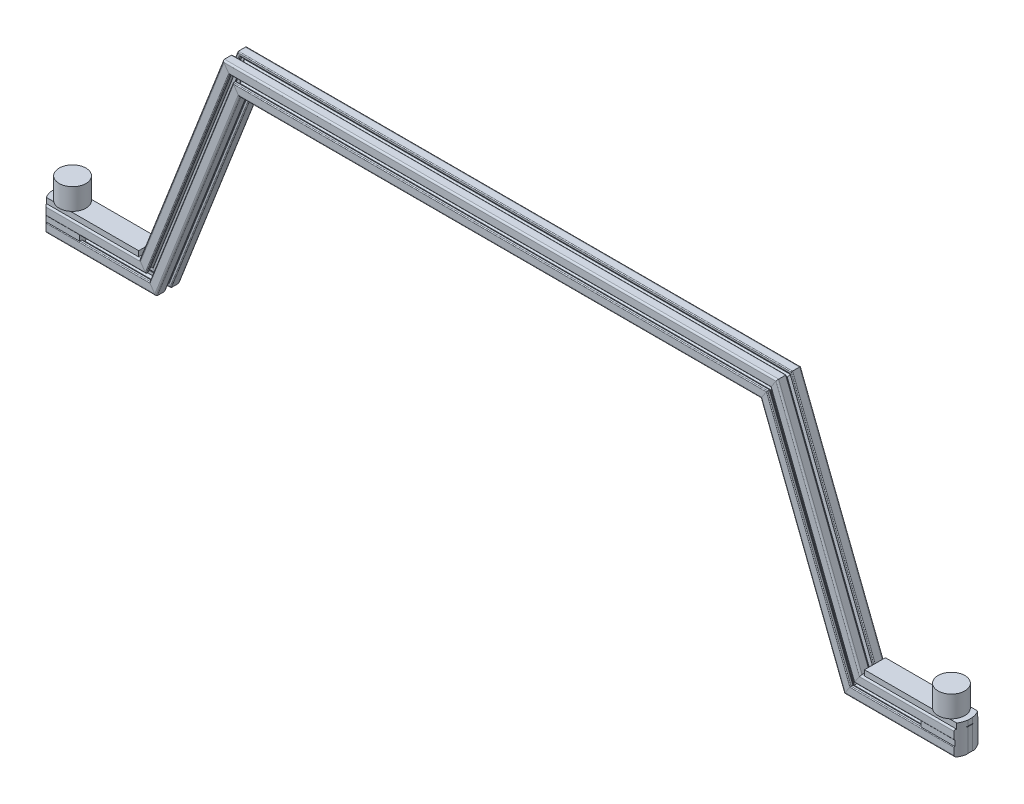
SolidWorks part; units mm, degrees
material "Commercially Pure CP-Ti UNS R50400 (SS)"
ref_plane "Front Plane" through (0, 0, 0) normal (0, 0, 1) x (1, 0, 0)
ref_plane "Top Plane" through (0, 0, 0) normal (0, 1, 0) x (1, 0, 0)
ref_plane "Right Plane" through (0, 0, 0) normal (1, 0, 0) x (0, 0, -1)
sketch "Sketch7" plane through (0, 0, 0) normal (1, 0, 0) x (0, 0, -1)
  line L0 (13.9698, 21.2743) -> (13.5298, 21.2743)
  line L1 (12.0298, 22.7743) -> (12.0298, 23.2743)
  line L2 (13.5298, 24.7743) -> (23.1398, 24.7743)
  line L3 (25.4198, 22.4943) -> (25.4198, 12.8843)
  line L4 (23.9198, 11.3843) -> (23.4198, 11.3843)
  line L5 (21.9198, 12.8843) -> (21.9198, 13.3243)
  line L6 (20.9198, 14.3243) -> (15.3498, 14.3243)
  line L7 (14.9698, 14.7043) -> (14.9698, 20.2743)
  line L8 (21.9589, -6.6897) -> (21.9589, -6.2497)
  line L9 (23.4589, -4.7497) -> (23.9589, -4.7497)
  line L10 (25.4589, -6.2497) -> (25.4589, -15.8597)
  line L11 (23.1789, -18.1397) -> (13.5689, -18.1397)
  line L12 (12.0689, -16.6397) -> (12.0689, -16.1397)
  line L13 (13.5689, -14.6397) -> (14.0089, -14.6397)
  line L14 (15.0089, -13.6397) -> (15.0089, -8.0697)
  line L15 (15.3889, -7.6897) -> (20.9589, -7.6897)
  line L16 (-6.0052, -14.6787) -> (-5.5652, -14.6787)
  line L17 (-4.0652, -16.1787) -> (-4.0652, -16.6787)
  line L18 (-5.5652, -18.1787) -> (-15.1752, -18.1787)
  line L19 (-17.4552, -15.8987) -> (-17.4552, -6.2887)
  line L20 (-15.9552, -4.7887) -> (-15.4552, -4.7887)
  line L21 (-13.9552, -6.2887) -> (-13.9552, -6.7287)
  line L22 (-12.9552, -7.7287) -> (-7.3852, -7.7287)
  line L23 (-7.0052, -8.1087) -> (-7.0052, -13.6787)
  line L24 (1.8289, -2.4886) -> (1.4132, -2.3164)
  line L25 (-1.632, 0.7289) -> (-1.8042, 1.1447)
  line L26 (-1.804, 5.4512) -> (-1.6318, 5.867)
  line L27 (1.4134, 8.9121) -> (1.8292, 9.0843)
  line L28 (6.1358, 9.0842) -> (6.5515, 8.912)
  line L29 (9.5966, 5.8667) -> (9.7688, 5.451)
  line L30 (9.7687, 1.1444) -> (9.5965, 0.7287)
  line L31 (6.5512, -2.3165) -> (6.1355, -2.4887)
  line L32 (-13.9942, 13.2853) -> (-13.9942, 12.8453)
  line L33 (-15.4942, 11.3453) -> (-15.9942, 11.3453)
  line L34 (-17.4942, 12.8453) -> (-17.4942, 22.4553)
  line L35 (-15.2142, 24.7353) -> (-5.6042, 24.7353)
  line L36 (-4.1042, 23.2353) -> (-4.1042, 22.7353)
  line L37 (-5.6042, 21.2353) -> (-6.0442, 21.2353)
  line L38 (-7.0442, 20.2353) -> (-7.0442, 14.6653)
  line L39 (-7.4242, 14.2853) -> (-12.9942, 14.2853)
  line L40 (4.9058, 11.2153) -> (4.0058, 10.7002)
  line L41 (4.0058, 10.7002) -> (3.1058, 11.2153)
  line L42 (3.1058, 11.2153) -> (-2.1975, 11.2153)
  line L43 (-2.4662, 11.3266) -> (-5.9329, 14.7933)
  line L44 (-6.0442, 15.062) -> (-6.0442, 19.3553)
  line L45 (-5.6642, 19.7353) -> (-2.5792, 19.7353)
  line L46 (-1.0592, 21.2553) -> (-1.0592, 24.2153)
  line L47 (-2.5792, 25.7353) -> (-15.4942, 25.7353)
  line L48 (-18.4942, 22.7353) -> (-18.4942, 9.8203)
  line L49 (-16.9742, 8.3003) -> (-14.0142, 8.3003)
  line L50 (-12.4942, 9.8203) -> (-12.4942, 12.9053)
  line L51 (-12.1142, 13.2853) -> (-7.8138, 13.2853)
  line L52 (-7.5451, 13.174) -> (-4.0855, 9.7144)
  line L53 (-3.9742, 9.4457) -> (-3.9742, 4.1353)
  line L54 (-3.9742, 4.1353) -> (-3.4546, 3.2353)
  line L55 (-3.4546, 3.2353) -> (-3.9742, 2.3353)
  line L56 (-3.9742, 2.3353) -> (-3.9742, -2.968)
  line L57 (-4.0855, -3.2367) -> (-7.5522, -6.7034)
  line L58 (-7.8209, -6.8147) -> (-12.1142, -6.8147)
  line L59 (-12.4942, -6.4347) -> (-12.4942, -3.3497)
  line L60 (-14.0142, -1.8297) -> (-16.9742, -1.8297)
  line L61 (-18.4942, -3.3497) -> (-18.4942, -16.2647)
  line L62 (-15.4942, -19.2647) -> (-2.5792, -19.2647)
  line L63 (-1.0592, -17.7447) -> (-1.0592, -14.7847)
  line L64 (-2.5792, -13.2647) -> (-5.6642, -13.2647)
  line L65 (-6.0442, -12.8847) -> (-6.0442, -8.5843)
  line L66 (-5.9329, -8.3156) -> (-2.4733, -4.856)
  line L67 (-2.2046, -4.7447) -> (3.1058, -4.7447)
  line L68 (3.1058, -4.7447) -> (4.0058, -4.2295)
  line L69 (4.0058, -4.2295) -> (4.9058, -4.7447)
  line L70 (4.9058, -4.7447) -> (10.2091, -4.7447)
  line L71 (10.4778, -4.856) -> (13.9445, -8.3227)
  line L72 (14.0558, -8.5914) -> (14.0558, -12.8847)
  line L73 (13.6758, -13.2647) -> (10.5908, -13.2647)
  line L74 (9.0708, -14.7847) -> (9.0708, -17.7447)
  line L75 (10.5908, -19.2647) -> (23.5058, -19.2647)
  line L76 (26.5058, -16.2647) -> (26.5058, -3.3497)
  line L77 (24.9858, -1.8297) -> (22.0258, -1.8297)
  line L78 (20.5058, -3.3497) -> (20.5058, -6.4347)
  line L79 (20.1258, -6.8147) -> (15.8254, -6.8147)
  line L80 (15.5567, -6.7034) -> (12.0971, -3.2438)
  line L81 (11.9858, -2.9751) -> (11.9858, 2.3353)
  line L82 (11.9858, 2.3353) -> (11.4662, 3.2353)
  line L83 (11.4662, 3.2353) -> (11.9858, 4.1353)
  line L84 (11.9858, 4.1353) -> (11.9858, 9.4386)
  line L85 (12.0971, 9.7073) -> (15.5638, 13.174)
  line L86 (15.8325, 13.2853) -> (20.1258, 13.2853)
  line L87 (20.5058, 12.9053) -> (20.5058, 9.8203)
  line L88 (22.0258, 8.3003) -> (24.9858, 8.3003)
  line L89 (26.5058, 9.8203) -> (26.5058, 22.7353)
  line L90 (23.5058, 25.7353) -> (10.5908, 25.7353)
  line L91 (9.0708, 24.2153) -> (9.0708, 21.2553)
  line L92 (10.5908, 19.7353) -> (13.6758, 19.7353)
  line L93 (14.0558, 19.3553) -> (14.0558, 15.0549)
  line L94 (13.9445, 14.7862) -> (10.4849, 11.3266)
  line L95 (10.2162, 11.2153) -> (4.9058, 11.2153)
  arc A0 (14.9698, 20.2743) -> (13.9698, 21.2743) centre (13.9698, 20.2743) ccw
  arc A1 (12.0298, 22.7743) -> (13.5298, 21.2743) centre (13.5298, 22.7743) ccw
  arc A2 (13.5298, 24.7743) -> (12.0298, 23.2743) centre (13.5298, 23.2743) ccw
  arc A3 (25.4198, 22.4943) -> (23.1398, 24.7743) centre (23.1398, 22.4943) ccw
  arc A4 (23.9198, 11.3843) -> (25.4198, 12.8843) centre (23.9198, 12.8843) ccw
  arc A5 (21.9198, 12.8843) -> (23.4198, 11.3843) centre (23.4198, 12.8843) ccw
  arc A6 (21.9198, 13.3243) -> (20.9198, 14.3243) centre (20.9198, 13.3243) ccw
  arc A7 (14.9698, 14.7043) -> (15.3498, 14.3243) centre (15.3498, 14.7043) ccw
  arc A8 (20.9589, -7.6897) -> (21.9589, -6.6897) centre (20.9589, -6.6897) ccw
  arc A9 (23.4589, -4.7497) -> (21.9589, -6.2497) centre (23.4589, -6.2497) ccw
  arc A10 (25.4589, -6.2497) -> (23.9589, -4.7497) centre (23.9589, -6.2497) ccw
  arc A11 (23.1789, -18.1397) -> (25.4589, -15.8597) centre (23.1789, -15.8597) ccw
  arc A12 (12.0689, -16.6397) -> (13.5689, -18.1397) centre (13.5689, -16.6397) ccw
  arc A13 (13.5689, -14.6397) -> (12.0689, -16.1397) centre (13.5689, -16.1397) ccw
  arc A14 (14.0089, -14.6397) -> (15.0089, -13.6397) centre (14.0089, -13.6397) ccw
  arc A15 (15.3889, -7.6897) -> (15.0089, -8.0697) centre (15.3889, -8.0697) ccw
  arc A16 (-7.0052, -13.6787) -> (-6.0052, -14.6787) centre (-6.0052, -13.6787) ccw
  arc A17 (-4.0652, -16.1787) -> (-5.5652, -14.6787) centre (-5.5652, -16.1787) ccw
  arc A18 (-5.5652, -18.1787) -> (-4.0652, -16.6787) centre (-5.5652, -16.6787) ccw
  arc A19 (-17.4552, -15.8987) -> (-15.1752, -18.1787) centre (-15.1752, -15.8987) ccw
  arc A20 (-15.9552, -4.7887) -> (-17.4552, -6.2887) centre (-15.9552, -6.2887) ccw
  arc A21 (-13.9552, -6.2887) -> (-15.4552, -4.7887) centre (-15.4552, -6.2887) ccw
  arc A22 (-13.9552, -6.7287) -> (-12.9552, -7.7287) centre (-12.9552, -6.7287) ccw
  arc A23 (-7.0052, -8.1087) -> (-7.3852, -7.7287) centre (-7.3852, -8.1087) ccw
  arc A24 (1.0363, -0.7421) -> (1.4132, -2.3164) centre (1.7959, -1.3925) ccw
  arc A25 (-0.0577, 0.352) -> (1.0363, -0.7421) centre (3.9823, 3.2978) ccw
  arc A26 (-1.632, 0.7289) -> (-0.0577, 0.352) centre (-0.7081, 1.1116) ccw
  arc A27 (-0.9575, 2.5244) -> (-1.8042, 1.1447) centre (-0.8803, 1.5274) ccw
  arc A28 (-0.9574, 4.0715) -> (-0.9575, 2.5244) centre (3.9823, 3.2978) ccw
  arc A29 (-1.804, 5.4512) -> (-0.9574, 4.0715) centre (-0.8802, 5.0686) ccw
  arc A30 (-0.0575, 6.2439) -> (-1.6318, 5.867) centre (-0.708, 5.4843) ccw
  arc A31 (1.0365, 7.3379) -> (-0.0575, 6.2439) centre (3.9823, 3.2978) ccw
  arc A32 (1.4134, 8.9121) -> (1.0365, 7.3379) centre (1.7961, 7.9882) ccw
  arc A33 (3.2089, 8.2376) -> (1.8292, 9.0843) centre (2.2119, 8.1604) ccw
  arc A34 (4.7561, 8.2376) -> (3.2089, 8.2376) centre (3.9823, 3.2978) ccw
  arc A35 (6.1358, 9.0842) -> (4.7561, 8.2376) centre (5.7531, 8.1603) ccw
  arc A36 (6.9284, 7.3377) -> (6.5515, 8.912) centre (6.1688, 7.9881) ccw
  arc A37 (8.0224, 6.2437) -> (6.9284, 7.3377) centre (3.9823, 3.2978) ccw
  arc A38 (9.5966, 5.8667) -> (8.0224, 6.2437) centre (8.6727, 5.484) ccw
  arc A39 (8.9222, 4.0713) -> (9.7688, 5.451) centre (8.845, 5.0683) ccw
  arc A40 (8.9221, 2.5241) -> (8.9222, 4.0713) centre (3.9823, 3.2978) ccw
  arc A41 (9.7687, 1.1444) -> (8.9221, 2.5241) centre (8.8448, 1.5271) ccw
  arc A42 (8.0222, 0.3518) -> (9.5965, 0.7287) centre (8.6726, 1.1113) ccw
  arc A43 (6.9282, -0.7422) -> (8.0222, 0.3518) centre (3.9823, 3.2978) ccw
  arc A44 (6.5512, -2.3165) -> (6.9282, -0.7422) centre (6.1685, -1.3926) ccw
  arc A45 (4.7558, -1.642) -> (6.1355, -2.4887) centre (5.7528, -1.5648) ccw
  arc A46 (3.2086, -1.642) -> (4.7558, -1.642) centre (3.9823, 3.2978) ccw
  arc A47 (1.8289, -2.4886) -> (3.2086, -1.642) centre (2.2116, -1.5647) ccw
  arc A48 (-12.9942, 14.2853) -> (-13.9942, 13.2853) centre (-12.9942, 13.2853) ccw
  arc A49 (-15.4942, 11.3453) -> (-13.9942, 12.8453) centre (-15.4942, 12.8453) ccw
  arc A50 (-17.4942, 12.8453) -> (-15.9942, 11.3453) centre (-15.9942, 12.8453) ccw
  arc A51 (-15.2142, 24.7353) -> (-17.4942, 22.4553) centre (-15.2142, 22.4553) ccw
  arc A52 (-4.1042, 23.2353) -> (-5.6042, 24.7353) centre (-5.6042, 23.2353) ccw
  arc A53 (-5.6042, 21.2353) -> (-4.1042, 22.7353) centre (-5.6042, 22.7353) ccw
  arc A54 (-6.0442, 21.2353) -> (-7.0442, 20.2353) centre (-6.0442, 20.2353) ccw
  arc A55 (-7.4242, 14.2853) -> (-7.0442, 14.6653) centre (-7.4242, 14.6653) ccw
  arc A56 (-2.4662, 11.3266) -> (-2.1975, 11.2153) centre (-2.1975, 11.5953) ccw
  arc A57 (-6.0442, 15.062) -> (-5.9329, 14.7933) centre (-5.6642, 15.062) ccw
  arc A58 (-5.6642, 19.7353) -> (-6.0442, 19.3553) centre (-5.6642, 19.3553) ccw
  arc A59 (-2.5792, 19.7353) -> (-1.0592, 21.2553) centre (-2.5792, 21.2553) ccw
  arc A60 (-1.0592, 24.2153) -> (-2.5792, 25.7353) centre (-2.5792, 24.2153) ccw
  arc A61 (-15.4942, 25.7353) -> (-18.4942, 22.7353) centre (-15.4942, 22.7353) ccw
  arc A62 (-18.4942, 9.8203) -> (-16.9742, 8.3003) centre (-16.9742, 9.8203) ccw
  arc A63 (-14.0142, 8.3003) -> (-12.4942, 9.8203) centre (-14.0142, 9.8203) ccw
  arc A64 (-12.1142, 13.2853) -> (-12.4942, 12.9053) centre (-12.1142, 12.9053) ccw
  arc A65 (-7.5451, 13.174) -> (-7.8138, 13.2853) centre (-7.8138, 12.9053) ccw
  arc A66 (-3.9742, 9.4457) -> (-4.0855, 9.7144) centre (-4.3542, 9.4457) ccw
  arc A67 (-4.0855, -3.2367) -> (-3.9742, -2.968) centre (-4.3542, -2.968) ccw
  arc A68 (-7.8209, -6.8147) -> (-7.5522, -6.7034) centre (-7.8209, -6.4347) ccw
  arc A69 (-12.4942, -6.4347) -> (-12.1142, -6.8147) centre (-12.1142, -6.4347) ccw
  arc A70 (-12.4942, -3.3497) -> (-14.0142, -1.8297) centre (-14.0142, -3.3497) ccw
  arc A71 (-16.9742, -1.8297) -> (-18.4942, -3.3497) centre (-16.9742, -3.3497) ccw
  arc A72 (-18.4942, -16.2647) -> (-15.4942, -19.2647) centre (-15.4942, -16.2647) ccw
  arc A73 (-2.5792, -19.2647) -> (-1.0592, -17.7447) centre (-2.5792, -17.7447) ccw
  arc A74 (-1.0592, -14.7847) -> (-2.5792, -13.2647) centre (-2.5792, -14.7847) ccw
  arc A75 (-6.0442, -12.8847) -> (-5.6642, -13.2647) centre (-5.6642, -12.8847) ccw
  arc A76 (-5.9329, -8.3156) -> (-6.0442, -8.5843) centre (-5.6642, -8.5843) ccw
  arc A77 (-2.2046, -4.7447) -> (-2.4733, -4.856) centre (-2.2046, -5.1247) ccw
  arc A78 (10.4778, -4.856) -> (10.2091, -4.7447) centre (10.2091, -5.1247) ccw
  arc A79 (14.0558, -8.5914) -> (13.9445, -8.3227) centre (13.6758, -8.5914) ccw
  arc A80 (13.6758, -13.2647) -> (14.0558, -12.8847) centre (13.6758, -12.8847) ccw
  arc A81 (10.5908, -13.2647) -> (9.0708, -14.7847) centre (10.5908, -14.7847) ccw
  arc A82 (9.0708, -17.7447) -> (10.5908, -19.2647) centre (10.5908, -17.7447) ccw
  arc A83 (23.5058, -19.2647) -> (26.5058, -16.2647) centre (23.5058, -16.2647) ccw
  arc A84 (26.5058, -3.3497) -> (24.9858, -1.8297) centre (24.9858, -3.3497) ccw
  arc A85 (22.0258, -1.8297) -> (20.5058, -3.3497) centre (22.0258, -3.3497) ccw
  arc A86 (20.1258, -6.8147) -> (20.5058, -6.4347) centre (20.1258, -6.4347) ccw
  arc A87 (15.5567, -6.7034) -> (15.8254, -6.8147) centre (15.8254, -6.4347) ccw
  arc A88 (11.9858, -2.9751) -> (12.0971, -3.2438) centre (12.3658, -2.9751) ccw
  arc A89 (12.0971, 9.7073) -> (11.9858, 9.4386) centre (12.3658, 9.4386) ccw
  arc A90 (15.8325, 13.2853) -> (15.5638, 13.174) centre (15.8325, 12.9053) ccw
  arc A91 (20.5058, 12.9053) -> (20.1258, 13.2853) centre (20.1258, 12.9053) ccw
  arc A92 (20.5058, 9.8203) -> (22.0258, 8.3003) centre (22.0258, 9.8203) ccw
  arc A93 (24.9858, 8.3003) -> (26.5058, 9.8203) centre (24.9858, 9.8203) ccw
  arc A94 (26.5058, 22.7353) -> (23.5058, 25.7353) centre (23.5058, 22.7353) ccw
  arc A95 (10.5908, 25.7353) -> (9.0708, 24.2153) centre (10.5908, 24.2153) ccw
  arc A96 (9.0708, 21.2553) -> (10.5908, 19.7353) centre (10.5908, 21.2553) ccw
  arc A97 (14.0558, 19.3553) -> (13.6758, 19.7353) centre (13.6758, 19.3553) ccw
  arc A98 (13.9445, 14.7862) -> (14.0558, 15.0549) centre (13.6758, 15.0549) ccw
  arc A99 (10.2162, 11.2153) -> (10.4849, 11.3266) centre (10.2162, 11.5953) ccw
sketch "Sketch1" plane through (0, 0, 0) normal (0, 0, 1) x (1, 0, 0)
  line L0 (0, 0) -> (200, 0)
  line L1 (200, 0) -> (355.8974, 400)
  line L2 (355.8974, 400) -> (855.8974, 400)
  dimension "D1" = 500
  dimension "D2" = 200
  dimension "D3" = 400
sketch "Sketch2" [suppressed] plane through (0, 0, 0) normal (1, 0, 0) x (0, 0, -1)
  line L0 (-33.5, -41) -> (-31.5, -41)
  line L1 (-31.5, -43) -> (-42, -43)
  line L2 (-43, -42) -> (-43, -31.5)
  line L3 (-41, -31.5) -> (-41, -33.5)
  line L4 (-40, -34.5) -> (-34.88, -34.5)
  line L5 (-34.5, -34.88) -> (-34.5, -40)
  line L6 (-16.657, -26.2238) -> (-18.284, -25.188)
  line L7 (-19.8123, -26.7162) -> (-18.7764, -28.3429)
  line L8 (-21.0015, -29.2647) -> (-21.4195, -27.3819)
  line L9 (-23.5808, -27.3818) -> (-23.9986, -29.2645)
  line L10 (-26.2238, -28.343) -> (-25.188, -26.716)
  line L11 (-26.7162, -25.1877) -> (-28.3429, -26.2236)
  line L12 (-29.2647, -23.9985) -> (-27.3819, -23.5805)
  line L13 (-27.3818, -21.4192) -> (-29.2645, -21.0014)
  line L14 (-28.343, -18.7762) -> (-26.716, -19.812)
  line L15 (-25.1877, -18.2838) -> (-26.2236, -16.6571)
  line L16 (-23.9985, -15.7353) -> (-23.5805, -17.6181)
  line L17 (-21.4192, -17.6182) -> (-21.0014, -15.7355)
  line L18 (-18.7762, -16.657) -> (-19.812, -18.284)
  line L19 (-18.2838, -19.8123) -> (-16.6571, -18.7764)
  line L20 (-15.7353, -21.0015) -> (-17.6181, -21.4195)
  line L21 (-17.6182, -23.5808) -> (-15.7355, -23.9986)
  line L22 (41, -33.5) -> (41, -31.5)
  line L23 (43, -31.5) -> (43, -42)
  line L24 (42, -43) -> (31.5, -43)
  line L25 (31.5, -41) -> (33.5, -41)
  line L26 (34.5, -40) -> (34.5, -34.88)
  line L27 (34.88, -34.5) -> (40, -34.5)
  line L28 (26.7162, -19.8123) -> (28.3429, -18.7764)
  line L29 (29.2647, -21.0015) -> (27.3819, -21.4195)
  line L30 (27.3818, -23.5808) -> (29.2645, -23.9986)
  line L31 (28.343, -26.2238) -> (26.716, -25.188)
  line L32 (25.1877, -26.7162) -> (26.2236, -28.3429)
  line L33 (23.9985, -29.2647) -> (23.5805, -27.3819)
  line L34 (21.4192, -27.3818) -> (21.0014, -29.2645)
  line L35 (18.7762, -28.343) -> (19.812, -26.716)
  line L36 (18.2838, -25.1877) -> (16.6571, -26.2236)
  line L37 (15.7353, -23.9985) -> (17.6181, -23.5805)
  line L38 (17.6182, -21.4192) -> (15.7355, -21.0014)
  line L39 (16.657, -18.7762) -> (18.284, -19.812)
  line L40 (19.8123, -18.2838) -> (18.7764, -16.6571)
  line L41 (21.0015, -15.7353) -> (21.4195, -17.6181)
  line L42 (23.5808, -17.6182) -> (23.9986, -15.7355)
  line L43 (26.2238, -16.657) -> (25.188, -18.284)
  line L44 (34.5, 34.88) -> (34.5, 40)
  line L45 (33.5, 41) -> (31.5, 41)
  line L46 (31.5, 43) -> (42, 43)
  line L47 (43, 42) -> (43, 31.5)
  line L48 (41, 31.5) -> (41, 33.5)
  line L49 (40, 34.5) -> (34.88, 34.5)
  line L50 (26.7162, 25.1877) -> (28.3429, 26.2236)
  line L51 (29.2647, 23.9985) -> (27.3819, 23.5805)
  line L52 (27.3818, 21.4192) -> (29.2645, 21.0014)
  line L53 (28.343, 18.7762) -> (26.716, 19.812)
  line L54 (25.1877, 18.2838) -> (26.2236, 16.6571)
  line L55 (23.9985, 15.7353) -> (23.5805, 17.6181)
  line L56 (21.4192, 17.6182) -> (21.0014, 15.7355)
  line L57 (18.7762, 16.657) -> (19.812, 18.284)
  line L58 (18.2838, 19.8123) -> (16.6571, 18.7764)
  line L59 (15.7353, 21.0015) -> (17.6181, 21.4195)
  line L60 (17.6182, 23.5808) -> (15.7355, 23.9986)
  line L61 (16.657, 26.2238) -> (18.284, 25.188)
  line L62 (19.8123, 26.7162) -> (18.7764, 28.3429)
  line L63 (21.0015, 29.2647) -> (21.4195, 27.3819)
  line L64 (23.5808, 27.3818) -> (23.9986, 29.2645)
  line L65 (26.2238, 28.343) -> (25.188, 26.716)
  line L66 (-41, 33.5) -> (-41, 31.5)
  line L67 (-43, 31.5) -> (-43, 42)
  line L68 (-42, 43) -> (-31.5, 43)
  line L69 (-31.5, 41) -> (-33.5, 41)
  line L70 (-34.5, 40) -> (-34.5, 34.88)
  line L71 (-34.88, 34.5) -> (-40, 34.5)
  line L72 (-16.657, 18.7762) -> (-18.284, 19.812)
  line L73 (-19.8123, 18.2838) -> (-18.7764, 16.6571)
  line L74 (-21.0015, 15.7353) -> (-21.4195, 17.6181)
  line L75 (-23.5808, 17.6182) -> (-23.9986, 15.7355)
  line L76 (-26.2238, 16.657) -> (-25.188, 18.284)
  line L77 (-26.7162, 19.8123) -> (-28.3429, 18.7764)
  line L78 (-29.2647, 21.0015) -> (-27.3819, 21.4195)
  line L79 (-27.3818, 23.5808) -> (-29.2645, 23.9986)
  line L80 (-28.343, 26.2238) -> (-26.716, 25.188)
  line L81 (-25.1877, 26.7162) -> (-26.2236, 28.3429)
  line L82 (-23.9985, 29.2647) -> (-23.5805, 27.3819)
  line L83 (-21.4192, 27.3818) -> (-21.0014, 29.2645)
  line L84 (-18.7762, 28.343) -> (-19.812, 26.716)
  line L85 (-18.2838, 25.1877) -> (-16.6571, 26.2236)
  line L86 (-15.7353, 23.9985) -> (-17.6181, 23.5805)
  line L87 (-17.6182, 21.4192) -> (-15.7355, 21.0014)
  line L88 (39, -10.16) -> (33.3774, -10.16)
  line L89 (31.9632, -10.7458) -> (29.8203, -12.8887)
  line L90 (29.5516, -13) -> (23.4, -13)
  line L91 (23.4, -13) -> (22.5, -13.5151)
  line L92 (22.5, -13.5151) -> (21.6, -13)
  line L93 (21.6, -13) -> (15, -13)
  line L94 (13, -15) -> (13, -21.6)
  line L95 (13, -21.6) -> (13.5196, -22.5)
  line L96 (13.5196, -22.5) -> (13, -23.4)
  line L97 (13, -23.4) -> (13, -29.5516)
  line L98 (12.8887, -29.8203) -> (11.3787, -31.3303)
  line L99 (10.5, -33.4516) -> (10.5, -40)
  line L100 (11.5, -41) -> (13.5, -41)
  line L101 (13.5, -43) -> (-13.5, -43)
  line L102 (-13.5, -41) -> (-11.5, -41)
  line L103 (-10.5, -40) -> (-10.5, -33.4516)
  line L104 (-11.3787, -31.3303) -> (-12.8887, -29.8203)
  line L105 (-13, -29.5516) -> (-13, -23.4)
  line L106 (-13, -23.4) -> (-13.5196, -22.5)
  line L107 (-13.5196, -22.5) -> (-13, -21.6)
  line L108 (-13, -21.6) -> (-13, -15)
  line L109 (-15, -13) -> (-21.6, -13)
  line L110 (-21.6, -13) -> (-22.5, -13.5151)
  line L111 (-22.5, -13.5151) -> (-23.4, -13)
  line L112 (-23.4, -13) -> (-29.5516, -13)
  line L113 (-29.8203, -12.8887) -> (-31.9632, -10.7458)
  line L114 (-33.3774, -10.16) -> (-39, -10.16)
  line L115 (-41, -12.16) -> (-41, -13.5)
  line L116 (-43, -13.5) -> (-43, 13.5)
  line L117 (-41, 13.5) -> (-41, 12.16)
  line L118 (-39, 10.16) -> (-33.3774, 10.16)
  line L119 (-31.9632, 10.7458) -> (-29.8203, 12.8887)
  line L120 (-29.5516, 13) -> (-23.4, 13)
  line L121 (-23.4, 13) -> (-22.5, 13.5151)
  line L122 (-22.5, 13.5151) -> (-21.6, 13)
  line L123 (-21.6, 13) -> (-15, 13)
  line L124 (-13, 15) -> (-13, 21.6)
  line L125 (-13, 21.6) -> (-13.5196, 22.5)
  line L126 (-13.5196, 22.5) -> (-13, 23.4)
  line L127 (-13, 23.4) -> (-13, 29.5516)
  line L128 (-12.8887, 29.8203) -> (-11.3787, 31.3303)
  line L129 (-10.5, 33.4516) -> (-10.5, 40)
  line L130 (-11.5, 41) -> (-13.5, 41)
  line L131 (-13.5, 43) -> (13.5, 43)
  line L132 (13.5, 41) -> (11.5, 41)
  line L133 (10.5, 40) -> (10.5, 33.4516)
  line L134 (11.3787, 31.3303) -> (12.8887, 29.8203)
  line L135 (13, 29.5516) -> (13, 23.4)
  line L136 (13, 23.4) -> (13.5196, 22.5)
  line L137 (13.5196, 22.5) -> (13, 21.6)
  line L138 (13, 21.6) -> (13, 15)
  line L139 (15, 13) -> (21.6, 13)
  line L140 (21.6, 13) -> (22.5, 13.5151)
  line L141 (22.5, 13.5151) -> (23.4, 13)
  line L142 (23.4, 13) -> (29.5516, 13)
  line L143 (29.8203, 12.8887) -> (31.9581, 10.7509)
  line L144 (33.3723, 10.1651) -> (39, 10.1651)
  line L145 (41, 12.1651) -> (41, 13.5)
  line L146 (43, 13.5) -> (43, -13.5)
  line L147 (41, -13.5) -> (41, -12.16)
  line L148 (45, -15.915) -> (45, 15.915)
  line L149 (43.48, 17.435) -> (40.52, 17.435)
  line L150 (39, 15.915) -> (39, 13.45)
  line L151 (38, 12.45) -> (34.9984, 12.45)
  line L152 (34.7297, 12.5613) -> (32.1113, 15.1797)
  line L153 (32, 15.4484) -> (32, 21.6)
  line L154 (32, 21.6) -> (31.4804, 22.5)
  line L155 (31.4804, 22.5) -> (32, 23.4)
  line L156 (32, 23.4) -> (32, 29.5516)
  line L157 (32.1113, 29.8203) -> (34.7297, 32.4387)
  line L158 (34.9984, 32.55) -> (38, 32.55)
  line L159 (39, 31.55) -> (39, 29.085)
  line L160 (40.52, 27.565) -> (43.48, 27.565)
  line L161 (45, 29.085) -> (45, 42)
  line L162 (42, 45) -> (29.085, 45)
  line L163 (27.565, 43.48) -> (27.565, 40.52)
  line L164 (29.085, 39) -> (31.55, 39)
  line L165 (32.55, 38) -> (32.55, 34.9984)
  line L166 (32.4387, 34.7297) -> (29.8203, 32.1113)
  line L167 (29.5516, 32) -> (23.4, 32)
  line L168 (23.4, 32) -> (22.5, 31.4849)
  line L169 (22.5, 31.4849) -> (21.6, 32)
  line L170 (21.6, 32) -> (15.4484, 32)
  line L171 (15.1797, 32.1113) -> (12.5613, 34.7297)
  line L172 (12.45, 34.9984) -> (12.45, 38)
  line L173 (13.45, 39) -> (15.915, 39)
  line L174 (17.435, 40.52) -> (17.435, 43.48)
  line L175 (15.915, 45) -> (-15.915, 45)
  line L176 (-17.435, 43.48) -> (-17.435, 40.52)
  line L177 (-15.915, 39) -> (-13.45, 39)
  line L178 (-12.45, 38) -> (-12.45, 34.9984)
  line L179 (-12.5613, 34.7297) -> (-15.1797, 32.1113)
  line L180 (-15.4484, 32) -> (-21.6, 32)
  line L181 (-21.6, 32) -> (-22.5, 31.4849)
  line L182 (-22.5, 31.4849) -> (-23.4, 32)
  line L183 (-23.4, 32) -> (-29.5516, 32)
  line L184 (-29.8203, 32.1113) -> (-32.4387, 34.7297)
  line L185 (-32.55, 34.9984) -> (-32.55, 38)
  line L186 (-31.55, 39) -> (-29.085, 39)
  line L187 (-27.565, 40.52) -> (-27.565, 43.48)
  line L188 (-29.085, 45) -> (-42, 45)
  line L189 (-45, 42) -> (-45, 29.085)
  line L190 (-43.48, 27.565) -> (-40.52, 27.565)
  line L191 (-39, 29.085) -> (-39, 31.55)
  line L192 (-38, 32.55) -> (-34.9984, 32.55)
  line L193 (-34.7297, 32.4387) -> (-32.1113, 29.8203)
  line L194 (-32, 29.5516) -> (-32, 23.4)
  line L195 (-32, 23.4) -> (-31.4804, 22.5)
  line L196 (-31.4804, 22.5) -> (-32, 21.6)
  line L197 (-32, 21.6) -> (-32, 15.4484)
  line L198 (-32.1113, 15.1797) -> (-34.7297, 12.5613)
  line L199 (-34.9984, 12.45) -> (-38, 12.45)
  line L200 (-39, 13.45) -> (-39, 15.915)
  line L201 (-40.52, 17.435) -> (-43.48, 17.435)
  line L202 (-45, 15.915) -> (-45, -15.915)
  line L203 (-43.48, -17.435) -> (-40.52, -17.435)
  line L204 (-39, -15.915) -> (-39, -13.45)
  line L205 (-38, -12.45) -> (-34.9984, -12.45)
  line L206 (-34.7297, -12.5613) -> (-32.1113, -15.1797)
  line L207 (-32, -15.4484) -> (-32, -21.6)
  line L208 (-32, -21.6) -> (-31.4804, -22.5)
  line L209 (-31.4804, -22.5) -> (-32, -23.4)
  line L210 (-32, -23.4) -> (-32, -29.5516)
  line L211 (-32.1113, -29.8203) -> (-34.7297, -32.4387)
  line L212 (-34.9984, -32.55) -> (-38, -32.55)
  line L213 (-39, -31.55) -> (-39, -29.085)
  line L214 (-40.52, -27.565) -> (-43.48, -27.565)
  line L215 (-45, -29.085) -> (-45, -42)
  line L216 (-42, -45) -> (-29.085, -45)
  line L217 (-27.565, -43.48) -> (-27.565, -40.52)
  line L218 (-29.085, -39) -> (-31.55, -39)
  line L219 (-32.55, -38) -> (-32.55, -34.9984)
  line L220 (-32.4387, -34.7297) -> (-29.8203, -32.1113)
  line L221 (-29.5516, -32) -> (-23.4, -32)
  line L222 (-23.4, -32) -> (-22.5, -31.4849)
  line L223 (-22.5, -31.4849) -> (-21.6, -32)
  line L224 (-21.6, -32) -> (-15.4484, -32)
  line L225 (-15.1797, -32.1113) -> (-12.5613, -34.7297)
  line L226 (-12.45, -34.9984) -> (-12.45, -38)
  line L227 (-13.45, -39) -> (-15.915, -39)
  line L228 (-17.435, -40.52) -> (-17.435, -43.48)
  line L229 (-15.915, -45) -> (15.915, -45)
  line L230 (17.435, -43.48) -> (17.435, -40.52)
  line L231 (15.915, -39) -> (13.45, -39)
  line L232 (12.45, -38) -> (12.45, -34.9984)
  line L233 (12.5613, -34.7297) -> (15.1797, -32.1113)
  line L234 (15.4484, -32) -> (21.6, -32)
  line L235 (21.6, -32) -> (22.5, -31.4849)
  line L236 (22.5, -31.4849) -> (23.4, -32)
  line L237 (23.4, -32) -> (29.5516, -32)
  line L238 (29.8203, -32.1113) -> (32.4387, -34.7297)
  line L239 (32.55, -34.9984) -> (32.55, -38)
  line L240 (31.55, -39) -> (29.085, -39)
  line L241 (27.565, -40.52) -> (27.565, -43.48)
  line L242 (29.085, -45) -> (42, -45)
  line L243 (45, -42) -> (45, -29.085)
  line L244 (43.48, -27.565) -> (40.52, -27.565)
  line L245 (39, -29.085) -> (39, -31.55)
  line L246 (38, -32.55) -> (34.9984, -32.55)
  line L247 (34.7297, -32.4387) -> (32.1113, -29.8203)
  line L248 (32, -29.5516) -> (32, -23.4)
  line L249 (32, -23.4) -> (31.4804, -22.5)
  line L250 (31.4804, -22.5) -> (32, -21.6)
  line L251 (32, -21.6) -> (32, -15.4484)
  line L252 (32.1113, -15.1797) -> (34.7297, -12.5613)
  line L253 (34.9984, -12.45) -> (38, -12.45)
  line L254 (39, -13.45) -> (39, -15.915)
  line L255 (40.52, -17.435) -> (43.48, -17.435)
  arc A0 (-34.5, -40) -> (-33.5, -41) centre (-33.5, -40) ccw
  arc A1 (-31.5, -43) -> (-31.5, -41) centre (-31.5, -42) ccw
  arc A2 (-43, -42) -> (-42, -43) centre (-42, -42) ccw
  arc A3 (-41, -31.5) -> (-43, -31.5) centre (-42, -31.5) ccw
  arc A4 (-41, -33.5) -> (-40, -34.5) centre (-40, -33.5) ccw
  arc A5 (-34.5, -34.88) -> (-34.88, -34.5) centre (-34.88, -34.88) ccw
  arc A6 (-15.2086, -25.7917) -> (-15.0167, -25.3284) centre (-22.5, -22.5) ccw
  arc A7 (-16.657, -26.2238) -> (-15.2086, -25.7917) centre (-16.12, -25.3802) ccw
  arc A8 (-19.8123, -26.7162) -> (-18.284, -25.188) centre (-22.5, -22.5) ccw
  arc A9 (-19.2085, -29.7915) -> (-18.7764, -28.3429) centre (-19.6199, -28.8801) ccw
  arc A10 (-19.6717, -29.9834) -> (-19.2085, -29.7915) centre (-22.5, -22.5) ccw
  arc A11 (-21.0015, -29.2647) -> (-19.6717, -29.9834) centre (-20.0253, -29.048) ccw
  arc A12 (-23.5808, -27.3818) -> (-21.4195, -27.3819) centre (-22.5, -22.5) ccw
  arc A13 (-25.3284, -29.9833) -> (-23.9986, -29.2645) centre (-24.9749, -29.0479) ccw
  arc A14 (-25.7917, -29.7914) -> (-25.3284, -29.9833) centre (-22.5, -22.5) ccw
  arc A15 (-26.2238, -28.343) -> (-25.7917, -29.7914) centre (-25.3802, -28.88) ccw
  arc A16 (-26.7162, -25.1877) -> (-25.188, -26.716) centre (-22.5, -22.5) ccw
  arc A17 (-29.7915, -25.7915) -> (-28.3429, -26.2236) centre (-28.8801, -25.3801) ccw
  arc A18 (-29.9834, -25.3283) -> (-29.7915, -25.7915) centre (-22.5, -22.5) ccw
  arc A19 (-29.2647, -23.9985) -> (-29.9834, -25.3283) centre (-29.048, -24.9747) ccw
  arc A20 (-27.3818, -21.4192) -> (-27.3819, -23.5805) centre (-22.5, -22.5) ccw
  arc A21 (-29.9833, -19.6716) -> (-29.2645, -21.0014) centre (-29.0479, -20.0251) ccw
  arc A22 (-29.7914, -19.2083) -> (-29.9833, -19.6716) centre (-22.5, -22.5) ccw
  arc A23 (-28.343, -18.7762) -> (-29.7914, -19.2083) centre (-28.88, -19.6198) ccw
  arc A24 (-25.1877, -18.2838) -> (-26.716, -19.812) centre (-22.5, -22.5) ccw
  arc A25 (-25.7915, -15.2085) -> (-26.2236, -16.6571) centre (-25.3801, -16.1199) ccw
  arc A26 (-25.3283, -15.0166) -> (-25.7915, -15.2085) centre (-22.5, -22.5) ccw
  arc A27 (-23.9985, -15.7353) -> (-25.3283, -15.0166) centre (-24.9747, -15.952) ccw
  arc A28 (-21.4192, -17.6182) -> (-23.5805, -17.6181) centre (-22.5, -22.5) ccw
  arc A29 (-19.6716, -15.0167) -> (-21.0014, -15.7355) centre (-20.0251, -15.9521) ccw
  arc A30 (-19.2083, -15.2086) -> (-19.6716, -15.0167) centre (-22.5, -22.5) ccw
  arc A31 (-18.7762, -16.657) -> (-19.2083, -15.2086) centre (-19.6198, -16.12) ccw
  arc A32 (-18.2838, -19.8123) -> (-19.812, -18.284) centre (-22.5, -22.5) ccw
  arc A33 (-15.2085, -19.2085) -> (-16.6571, -18.7764) centre (-16.1199, -19.6199) ccw
  arc A34 (-15.0166, -19.6717) -> (-15.2085, -19.2085) centre (-22.5, -22.5) ccw
  arc A35 (-15.7353, -21.0015) -> (-15.0166, -19.6717) centre (-15.952, -20.0253) ccw
  arc A36 (-17.6182, -23.5808) -> (-17.6181, -21.4195) centre (-22.5, -22.5) ccw
  arc A37 (-15.0167, -25.3284) -> (-15.7355, -23.9986) centre (-15.9521, -24.9749) ccw
  arc A38 (40, -34.5) -> (41, -33.5) centre (40, -33.5) ccw
  arc A39 (43, -31.5) -> (41, -31.5) centre (42, -31.5) ccw
  arc A40 (42, -43) -> (43, -42) centre (42, -42) ccw
  arc A41 (31.5, -41) -> (31.5, -43) centre (31.5, -42) ccw
  arc A42 (33.5, -41) -> (34.5, -40) centre (33.5, -40) ccw
  arc A43 (34.88, -34.5) -> (34.5, -34.88) centre (34.88, -34.88) ccw
  arc A44 (26.7162, -19.8123) -> (25.188, -18.284) centre (22.5, -22.5) ccw
  arc A45 (29.7915, -19.2085) -> (28.3429, -18.7764) centre (28.8801, -19.6199) ccw
  arc A46 (29.9834, -19.6717) -> (29.7915, -19.2085) centre (22.5, -22.5) ccw
  arc A47 (29.2647, -21.0015) -> (29.9834, -19.6717) centre (29.048, -20.0253) ccw
  arc A48 (27.3818, -23.5808) -> (27.3819, -21.4195) centre (22.5, -22.5) ccw
  arc A49 (29.9833, -25.3284) -> (29.2645, -23.9986) centre (29.0479, -24.9749) ccw
  arc A50 (29.7914, -25.7917) -> (29.9833, -25.3284) centre (22.5, -22.5) ccw
  arc A51 (28.343, -26.2238) -> (29.7914, -25.7917) centre (28.88, -25.3802) ccw
  arc A52 (25.1877, -26.7162) -> (26.716, -25.188) centre (22.5, -22.5) ccw
  arc A53 (25.7915, -29.7915) -> (26.2236, -28.3429) centre (25.3801, -28.8801) ccw
  arc A54 (25.3283, -29.9834) -> (25.7915, -29.7915) centre (22.5, -22.5) ccw
  arc A55 (23.9985, -29.2647) -> (25.3283, -29.9834) centre (24.9747, -29.048) ccw
  arc A56 (21.4192, -27.3818) -> (23.5805, -27.3819) centre (22.5, -22.5) ccw
  arc A57 (19.6716, -29.9833) -> (21.0014, -29.2645) centre (20.0251, -29.0479) ccw
  arc A58 (19.2083, -29.7914) -> (19.6716, -29.9833) centre (22.5, -22.5) ccw
  arc A59 (18.7762, -28.343) -> (19.2083, -29.7914) centre (19.6198, -28.88) ccw
  arc A60 (18.2838, -25.1877) -> (19.812, -26.716) centre (22.5, -22.5) ccw
  arc A61 (15.2085, -25.7915) -> (16.6571, -26.2236) centre (16.1199, -25.3801) ccw
  arc A62 (15.0166, -25.3283) -> (15.2085, -25.7915) centre (22.5, -22.5) ccw
  arc A63 (15.7353, -23.9985) -> (15.0166, -25.3283) centre (15.952, -24.9747) ccw
  arc A64 (17.6182, -21.4192) -> (17.6181, -23.5805) centre (22.5, -22.5) ccw
  arc A65 (15.0167, -19.6716) -> (15.7355, -21.0014) centre (15.9521, -20.0251) ccw
  arc A66 (15.2086, -19.2083) -> (15.0167, -19.6716) centre (22.5, -22.5) ccw
  arc A67 (16.657, -18.7762) -> (15.2086, -19.2083) centre (16.12, -19.6198) ccw
  arc A68 (19.8123, -18.2838) -> (18.284, -19.812) centre (22.5, -22.5) ccw
  arc A69 (19.2085, -15.2085) -> (18.7764, -16.6571) centre (19.6199, -16.1199) ccw
  arc A70 (19.6717, -15.0166) -> (19.2085, -15.2085) centre (22.5, -22.5) ccw
  arc A71 (21.0015, -15.7353) -> (19.6717, -15.0166) centre (20.0253, -15.952) ccw
  arc A72 (23.5808, -17.6182) -> (21.4195, -17.6181) centre (22.5, -22.5) ccw
  arc A73 (25.3284, -15.0167) -> (23.9986, -15.7355) centre (24.9749, -15.9521) ccw
  arc A74 (25.7917, -15.2086) -> (25.3284, -15.0167) centre (22.5, -22.5) ccw
  arc A75 (26.2238, -16.657) -> (25.7917, -15.2086) centre (25.3802, -16.12) ccw
  arc A76 (34.5, 34.88) -> (34.88, 34.5) centre (34.88, 34.88) ccw
  arc A77 (34.5, 40) -> (33.5, 41) centre (33.5, 40) ccw
  arc A78 (31.5, 43) -> (31.5, 41) centre (31.5, 42) ccw
  arc A79 (43, 42) -> (42, 43) centre (42, 42) ccw
  arc A80 (41, 31.5) -> (43, 31.5) centre (42, 31.5) ccw
  arc A81 (41, 33.5) -> (40, 34.5) centre (40, 33.5) ccw
  arc A82 (26.7162, 25.1877) -> (25.188, 26.716) centre (22.5, 22.5) ccw
  arc A83 (29.7915, 25.7915) -> (28.3429, 26.2236) centre (28.8801, 25.3801) ccw
  arc A84 (29.9834, 25.3283) -> (29.7915, 25.7915) centre (22.5, 22.5) ccw
  arc A85 (29.2647, 23.9985) -> (29.9834, 25.3283) centre (29.048, 24.9747) ccw
  arc A86 (27.3818, 21.4192) -> (27.3819, 23.5805) centre (22.5, 22.5) ccw
  arc A87 (29.9833, 19.6716) -> (29.2645, 21.0014) centre (29.0479, 20.0251) ccw
  arc A88 (29.7914, 19.2083) -> (29.9833, 19.6716) centre (22.5, 22.5) ccw
  arc A89 (28.343, 18.7762) -> (29.7914, 19.2083) centre (28.88, 19.6198) ccw
  arc A90 (25.1877, 18.2838) -> (26.716, 19.812) centre (22.5, 22.5) ccw
  arc A91 (25.7915, 15.2085) -> (26.2236, 16.6571) centre (25.3801, 16.1199) ccw
  arc A92 (25.3283, 15.0166) -> (25.7915, 15.2085) centre (22.5, 22.5) ccw
  arc A93 (23.9985, 15.7353) -> (25.3283, 15.0166) centre (24.9747, 15.952) ccw
  arc A94 (21.4192, 17.6182) -> (23.5805, 17.6181) centre (22.5, 22.5) ccw
  arc A95 (19.6716, 15.0167) -> (21.0014, 15.7355) centre (20.0251, 15.9521) ccw
  arc A96 (19.2083, 15.2086) -> (19.6716, 15.0167) centre (22.5, 22.5) ccw
  arc A97 (18.7762, 16.657) -> (19.2083, 15.2086) centre (19.6198, 16.12) ccw
  arc A98 (18.2838, 19.8123) -> (19.812, 18.284) centre (22.5, 22.5) ccw
  arc A99 (15.2085, 19.2085) -> (16.6571, 18.7764) centre (16.1199, 19.6199) ccw
  arc A100 (15.0166, 19.6717) -> (15.2085, 19.2085) centre (22.5, 22.5) ccw
  arc A101 (15.7353, 21.0015) -> (15.0166, 19.6717) centre (15.952, 20.0253) ccw
  arc A102 (17.6182, 23.5808) -> (17.6181, 21.4195) centre (22.5, 22.5) ccw
  arc A103 (15.0167, 25.3284) -> (15.7355, 23.9986) centre (15.9521, 24.9749) ccw
  arc A104 (15.2086, 25.7917) -> (15.0167, 25.3284) centre (22.5, 22.5) ccw
  arc A105 (16.657, 26.2238) -> (15.2086, 25.7917) centre (16.12, 25.3802) ccw
  arc A106 (19.8123, 26.7162) -> (18.284, 25.188) centre (22.5, 22.5) ccw
  arc A107 (19.2085, 29.7915) -> (18.7764, 28.3429) centre (19.6199, 28.8801) ccw
  arc A108 (19.6717, 29.9834) -> (19.2085, 29.7915) centre (22.5, 22.5) ccw
  arc A109 (21.0015, 29.2647) -> (19.6717, 29.9834) centre (20.0253, 29.048) ccw
  arc A110 (23.5808, 27.3818) -> (21.4195, 27.3819) centre (22.5, 22.5) ccw
  arc A111 (25.3284, 29.9833) -> (23.9986, 29.2645) centre (24.9749, 29.0479) ccw
  arc A112 (25.7917, 29.7914) -> (25.3284, 29.9833) centre (22.5, 22.5) ccw
  arc A113 (26.2238, 28.343) -> (25.7917, 29.7914) centre (25.3802, 28.88) ccw
  arc A114 (-40, 34.5) -> (-41, 33.5) centre (-40, 33.5) ccw
  arc A115 (-43, 31.5) -> (-41, 31.5) centre (-42, 31.5) ccw
  arc A116 (-42, 43) -> (-43, 42) centre (-42, 42) ccw
  arc A117 (-31.5, 41) -> (-31.5, 43) centre (-31.5, 42) ccw
  arc A118 (-33.5, 41) -> (-34.5, 40) centre (-33.5, 40) ccw
  arc A119 (-34.88, 34.5) -> (-34.5, 34.88) centre (-34.88, 34.88) ccw
  arc A120 (-15.2086, 19.2083) -> (-15.0167, 19.6716) centre (-22.5, 22.5) ccw
  arc A121 (-16.657, 18.7762) -> (-15.2086, 19.2083) centre (-16.12, 19.6198) ccw
  arc A122 (-19.8123, 18.2838) -> (-18.284, 19.812) centre (-22.5, 22.5) ccw
  arc A123 (-19.2085, 15.2085) -> (-18.7764, 16.6571) centre (-19.6199, 16.1199) ccw
  arc A124 (-19.6717, 15.0166) -> (-19.2085, 15.2085) centre (-22.5, 22.5) ccw
  arc A125 (-21.0015, 15.7353) -> (-19.6717, 15.0166) centre (-20.0253, 15.952) ccw
  arc A126 (-23.5808, 17.6182) -> (-21.4195, 17.6181) centre (-22.5, 22.5) ccw
  arc A127 (-25.3284, 15.0167) -> (-23.9986, 15.7355) centre (-24.9749, 15.9521) ccw
  arc A128 (-25.7917, 15.2086) -> (-25.3284, 15.0167) centre (-22.5, 22.5) ccw
  arc A129 (-26.2238, 16.657) -> (-25.7917, 15.2086) centre (-25.3802, 16.12) ccw
  arc A130 (-26.7162, 19.8123) -> (-25.188, 18.284) centre (-22.5, 22.5) ccw
  arc A131 (-29.7915, 19.2085) -> (-28.3429, 18.7764) centre (-28.8801, 19.6199) ccw
  arc A132 (-29.9834, 19.6717) -> (-29.7915, 19.2085) centre (-22.5, 22.5) ccw
  arc A133 (-29.2647, 21.0015) -> (-29.9834, 19.6717) centre (-29.048, 20.0253) ccw
  arc A134 (-27.3818, 23.5808) -> (-27.3819, 21.4195) centre (-22.5, 22.5) ccw
  arc A135 (-29.9833, 25.3284) -> (-29.2645, 23.9986) centre (-29.0479, 24.9749) ccw
  arc A136 (-29.7914, 25.7917) -> (-29.9833, 25.3284) centre (-22.5, 22.5) ccw
  arc A137 (-28.343, 26.2238) -> (-29.7914, 25.7917) centre (-28.88, 25.3802) ccw
  arc A138 (-25.1877, 26.7162) -> (-26.716, 25.188) centre (-22.5, 22.5) ccw
  arc A139 (-25.7915, 29.7915) -> (-26.2236, 28.3429) centre (-25.3801, 28.8801) ccw
  arc A140 (-25.3283, 29.9834) -> (-25.7915, 29.7915) centre (-22.5, 22.5) ccw
  arc A141 (-23.9985, 29.2647) -> (-25.3283, 29.9834) centre (-24.9747, 29.048) ccw
  arc A142 (-21.4192, 27.3818) -> (-23.5805, 27.3819) centre (-22.5, 22.5) ccw
  arc A143 (-19.6716, 29.9833) -> (-21.0014, 29.2645) centre (-20.0251, 29.0479) ccw
  arc A144 (-19.2083, 29.7914) -> (-19.6716, 29.9833) centre (-22.5, 22.5) ccw
  arc A145 (-18.7762, 28.343) -> (-19.2083, 29.7914) centre (-19.6198, 28.88) ccw
  arc A146 (-18.2838, 25.1877) -> (-19.812, 26.716) centre (-22.5, 22.5) ccw
  arc A147 (-15.2085, 25.7915) -> (-16.6571, 26.2236) centre (-16.1199, 25.3801) ccw
  arc A148 (-15.0166, 25.3283) -> (-15.2085, 25.7915) centre (-22.5, 22.5) ccw
  arc A149 (-15.7353, 23.9985) -> (-15.0166, 25.3283) centre (-15.952, 24.9747) ccw
  arc A150 (-17.6182, 21.4192) -> (-17.6181, 23.5805) centre (-22.5, 22.5) ccw
  arc A151 (-15.0167, 19.6716) -> (-15.7355, 21.0014) centre (-15.9521, 20.0251) ccw
  arc A152 (41, -12.16) -> (39, -10.16) centre (39, -12.16) ccw
  arc A153 (33.3774, -10.16) -> (31.9632, -10.7458) centre (33.3774, -12.16) ccw
  arc A154 (29.5516, -13) -> (29.8203, -12.8887) centre (29.5516, -12.62) ccw
  arc A155 (15, -13) -> (13, -15) centre (15, -15) ccw
  arc A156 (12.8887, -29.8203) -> (13, -29.5516) centre (12.62, -29.5516) ccw
  arc A157 (11.3787, -31.3303) -> (10.5, -33.4516) centre (13.5, -33.4516) ccw
  arc A158 (10.5, -40) -> (11.5, -41) centre (11.5, -40) ccw
  arc A159 (13.5, -43) -> (13.5, -41) centre (13.5, -42) ccw
  arc A160 (-13.5, -41) -> (-13.5, -43) centre (-13.5, -42) ccw
  arc A161 (-11.5, -41) -> (-10.5, -40) centre (-11.5, -40) ccw
  arc A162 (-10.5, -33.4516) -> (-11.3787, -31.3303) centre (-13.5, -33.4516) ccw
  arc A163 (-13, -29.5516) -> (-12.8887, -29.8203) centre (-12.62, -29.5516) ccw
  arc A164 (-13, -15) -> (-15, -13) centre (-15, -15) ccw
  arc A165 (-29.8203, -12.8887) -> (-29.5516, -13) centre (-29.5516, -12.62) ccw
  arc A166 (-31.9632, -10.7458) -> (-33.3774, -10.16) centre (-33.3774, -12.16) ccw
  arc A167 (-39, -10.16) -> (-41, -12.16) centre (-39, -12.16) ccw
  arc A168 (-43, -13.5) -> (-41, -13.5) centre (-42, -13.5) ccw
  arc A169 (-41, 13.5) -> (-43, 13.5) centre (-42, 13.5) ccw
  arc A170 (-41, 12.16) -> (-39, 10.16) centre (-39, 12.16) ccw
  arc A171 (-33.3774, 10.16) -> (-31.9632, 10.7458) centre (-33.3774, 12.16) ccw
  arc A172 (-29.5516, 13) -> (-29.8203, 12.8887) centre (-29.5516, 12.62) ccw
  arc A173 (-15, 13) -> (-13, 15) centre (-15, 15) ccw
  arc A174 (-12.8887, 29.8203) -> (-13, 29.5516) centre (-12.62, 29.5516) ccw
  arc A175 (-11.3787, 31.3303) -> (-10.5, 33.4516) centre (-13.5, 33.4516) ccw
  arc A176 (-10.5, 40) -> (-11.5, 41) centre (-11.5, 40) ccw
  arc A177 (-13.5, 43) -> (-13.5, 41) centre (-13.5, 42) ccw
  arc A178 (13.5, 41) -> (13.5, 43) centre (13.5, 42) ccw
  arc A179 (11.5, 41) -> (10.5, 40) centre (11.5, 40) ccw
  arc A180 (10.5, 33.4516) -> (11.3787, 31.3303) centre (13.5, 33.4516) ccw
  arc A181 (13, 29.5516) -> (12.8887, 29.8203) centre (12.62, 29.5516) ccw
  arc A182 (13, 15) -> (15, 13) centre (15, 15) ccw
  arc A183 (29.8203, 12.8887) -> (29.5516, 13) centre (29.5516, 12.62) ccw
  arc A184 (31.9581, 10.7509) -> (33.3723, 10.1651) centre (33.3723, 12.1651) ccw
  arc A185 (39, 10.1651) -> (41, 12.1651) centre (39, 12.1651) ccw
  arc A186 (43, 13.5) -> (41, 13.5) centre (42, 13.5) ccw
  arc A187 (41, -13.5) -> (43, -13.5) centre (42, -13.5) ccw
  arc A188 (45, 15.915) -> (43.48, 17.435) centre (43.48, 15.915) ccw
  arc A189 (40.52, 17.435) -> (39, 15.915) centre (40.52, 15.915) ccw
  arc A190 (38, 12.45) -> (39, 13.45) centre (38, 13.45) ccw
  arc A191 (34.7297, 12.5613) -> (34.9984, 12.45) centre (34.9984, 12.83) ccw
  arc A192 (32, 15.4484) -> (32.1113, 15.1797) centre (32.38, 15.4484) ccw
  arc A193 (32.1113, 29.8203) -> (32, 29.5516) centre (32.38, 29.5516) ccw
  arc A194 (34.9984, 32.55) -> (34.7297, 32.4387) centre (34.9984, 32.17) ccw
  arc A195 (39, 31.55) -> (38, 32.55) centre (38, 31.55) ccw
  arc A196 (39, 29.085) -> (40.52, 27.565) centre (40.52, 29.085) ccw
  arc A197 (43.48, 27.565) -> (45, 29.085) centre (43.48, 29.085) ccw
  arc A198 (45, 42) -> (42, 45) centre (42, 42) ccw
  arc A199 (29.085, 45) -> (27.565, 43.48) centre (29.085, 43.48) ccw
  arc A200 (27.565, 40.52) -> (29.085, 39) centre (29.085, 40.52) ccw
  arc A201 (32.55, 38) -> (31.55, 39) centre (31.55, 38) ccw
  arc A202 (32.4387, 34.7297) -> (32.55, 34.9984) centre (32.17, 34.9984) ccw
  arc A203 (29.5516, 32) -> (29.8203, 32.1113) centre (29.5516, 32.38) ccw
  arc A204 (15.1797, 32.1113) -> (15.4484, 32) centre (15.4484, 32.38) ccw
  arc A205 (12.45, 34.9984) -> (12.5613, 34.7297) centre (12.83, 34.9984) ccw
  arc A206 (13.45, 39) -> (12.45, 38) centre (13.45, 38) ccw
  arc A207 (15.915, 39) -> (17.435, 40.52) centre (15.915, 40.52) ccw
  arc A208 (17.435, 43.48) -> (15.915, 45) centre (15.915, 43.48) ccw
  arc A209 (-15.915, 45) -> (-17.435, 43.48) centre (-15.915, 43.48) ccw
  arc A210 (-17.435, 40.52) -> (-15.915, 39) centre (-15.915, 40.52) ccw
  arc A211 (-12.45, 38) -> (-13.45, 39) centre (-13.45, 38) ccw
  arc A212 (-12.5613, 34.7297) -> (-12.45, 34.9984) centre (-12.83, 34.9984) ccw
  arc A213 (-15.4484, 32) -> (-15.1797, 32.1113) centre (-15.4484, 32.38) ccw
  arc A214 (-29.8203, 32.1113) -> (-29.5516, 32) centre (-29.5516, 32.38) ccw
  arc A215 (-32.55, 34.9984) -> (-32.4387, 34.7297) centre (-32.17, 34.9984) ccw
  arc A216 (-31.55, 39) -> (-32.55, 38) centre (-31.55, 38) ccw
  arc A217 (-29.085, 39) -> (-27.565, 40.52) centre (-29.085, 40.52) ccw
  arc A218 (-27.565, 43.48) -> (-29.085, 45) centre (-29.085, 43.48) ccw
  arc A219 (-42, 45) -> (-45, 42) centre (-42, 42) ccw
  arc A220 (-45, 29.085) -> (-43.48, 27.565) centre (-43.48, 29.085) ccw
  arc A221 (-40.52, 27.565) -> (-39, 29.085) centre (-40.52, 29.085) ccw
  arc A222 (-38, 32.55) -> (-39, 31.55) centre (-38, 31.55) ccw
  arc A223 (-34.7297, 32.4387) -> (-34.9984, 32.55) centre (-34.9984, 32.17) ccw
  arc A224 (-32, 29.5516) -> (-32.1113, 29.8203) centre (-32.38, 29.5516) ccw
  arc A225 (-32.1113, 15.1797) -> (-32, 15.4484) centre (-32.38, 15.4484) ccw
  arc A226 (-34.9984, 12.45) -> (-34.7297, 12.5613) centre (-34.9984, 12.83) ccw
  arc A227 (-39, 13.45) -> (-38, 12.45) centre (-38, 13.45) ccw
  arc A228 (-39, 15.915) -> (-40.52, 17.435) centre (-40.52, 15.915) ccw
  arc A229 (-43.48, 17.435) -> (-45, 15.915) centre (-43.48, 15.915) ccw
  arc A230 (-45, -15.915) -> (-43.48, -17.435) centre (-43.48, -15.915) ccw
  arc A231 (-40.52, -17.435) -> (-39, -15.915) centre (-40.52, -15.915) ccw
  arc A232 (-38, -12.45) -> (-39, -13.45) centre (-38, -13.45) ccw
  arc A233 (-34.7297, -12.5613) -> (-34.9984, -12.45) centre (-34.9984, -12.83) ccw
  arc A234 (-32, -15.4484) -> (-32.1113, -15.1797) centre (-32.38, -15.4484) ccw
  arc A235 (-32.1113, -29.8203) -> (-32, -29.5516) centre (-32.38, -29.5516) ccw
  arc A236 (-34.9984, -32.55) -> (-34.7297, -32.4387) centre (-34.9984, -32.17) ccw
  arc A237 (-39, -31.55) -> (-38, -32.55) centre (-38, -31.55) ccw
  arc A238 (-39, -29.085) -> (-40.52, -27.565) centre (-40.52, -29.085) ccw
  arc A239 (-43.48, -27.565) -> (-45, -29.085) centre (-43.48, -29.085) ccw
  arc A240 (-45, -42) -> (-42, -45) centre (-42, -42) ccw
  arc A241 (-29.085, -45) -> (-27.565, -43.48) centre (-29.085, -43.48) ccw
  arc A242 (-27.565, -40.52) -> (-29.085, -39) centre (-29.085, -40.52) ccw
  arc A243 (-32.55, -38) -> (-31.55, -39) centre (-31.55, -38) ccw
  arc A244 (-32.4387, -34.7297) -> (-32.55, -34.9984) centre (-32.17, -34.9984) ccw
  arc A245 (-29.5516, -32) -> (-29.8203, -32.1113) centre (-29.5516, -32.38) ccw
  arc A246 (-15.1797, -32.1113) -> (-15.4484, -32) centre (-15.4484, -32.38) ccw
  arc A247 (-12.45, -34.9984) -> (-12.5613, -34.7297) centre (-12.83, -34.9984) ccw
  arc A248 (-13.45, -39) -> (-12.45, -38) centre (-13.45, -38) ccw
  arc A249 (-15.915, -39) -> (-17.435, -40.52) centre (-15.915, -40.52) ccw
  arc A250 (-17.435, -43.48) -> (-15.915, -45) centre (-15.915, -43.48) ccw
  arc A251 (15.915, -45) -> (17.435, -43.48) centre (15.915, -43.48) ccw
  arc A252 (17.435, -40.52) -> (15.915, -39) centre (15.915, -40.52) ccw
  arc A253 (12.45, -38) -> (13.45, -39) centre (13.45, -38) ccw
  arc A254 (12.5613, -34.7297) -> (12.45, -34.9984) centre (12.83, -34.9984) ccw
  arc A255 (15.4484, -32) -> (15.1797, -32.1113) centre (15.4484, -32.38) ccw
  arc A256 (29.8203, -32.1113) -> (29.5516, -32) centre (29.5516, -32.38) ccw
  arc A257 (32.55, -34.9984) -> (32.4387, -34.7297) centre (32.17, -34.9984) ccw
  arc A258 (31.55, -39) -> (32.55, -38) centre (31.55, -38) ccw
  arc A259 (29.085, -39) -> (27.565, -40.52) centre (29.085, -40.52) ccw
  arc A260 (27.565, -43.48) -> (29.085, -45) centre (29.085, -43.48) ccw
  arc A261 (42, -45) -> (45, -42) centre (42, -42) ccw
  arc A262 (45, -29.085) -> (43.48, -27.565) centre (43.48, -29.085) ccw
  arc A263 (40.52, -27.565) -> (39, -29.085) centre (40.52, -29.085) ccw
  arc A264 (38, -32.55) -> (39, -31.55) centre (38, -31.55) ccw
  arc A265 (34.7297, -32.4387) -> (34.9984, -32.55) centre (34.9984, -32.17) ccw
  arc A266 (32, -29.5516) -> (32.1113, -29.8203) centre (32.38, -29.5516) ccw
  arc A267 (32.1113, -15.1797) -> (32, -15.4484) centre (32.38, -15.4484) ccw
  arc A268 (34.9984, -12.45) -> (34.7297, -12.5613) centre (34.9984, -12.83) ccw
  arc A269 (39, -13.45) -> (38, -12.45) centre (38, -13.45) ccw
  arc A270 (39, -15.915) -> (40.52, -17.435) centre (40.52, -15.915) ccw
  arc A271 (43.48, -17.435) -> (45, -15.915) centre (43.48, -15.915) ccw
sweep "Sweep1" add profiles "Sketch7" path "Sketch1"
ref_plane "Plane1" through (855.8974, 0, 0) normal (1, 0, 0) x (0, 0, -1)
sketch "Sketch3" plane through (0, 25.7353, 0) normal (0, 1, 0) x (1, 0, 0)
  line L0 (0, -15.4942) -> (182.4093, -15.4942) construction
  line L1 (0, 23.5058) -> (177.9565, 23.5058)
  line L2 (0, 23.5058) -> (0, -15.4942)
  line L3 (0, -15.4942) -> (177.9565, -15.4942)
  line L4 (177.9565, 23.5058) -> (177.9565, -15.4942)
  point P6 (0, 0)
  point P7 (0, 0)
  point P8 (177.9565, -38.3202)
  point P9 (0, 16.474)
  point P10 (0, 23.5058)
  point P12 (0, -36.908)
  point P13 (0, -15.4942)
extrude "Boss-Extrude1" add sketch "Sketch3" along normal blind 10
sketch "Sketch4" plane through (0, 35.7353, 0) normal (0, 1, 0) x (1, 0, 0)
  line L0 (0, 4.0058) -> (177.9565, 4.0058) construction
  line L1 (0, 23.5058) -> (0, -15.4942) construction
  line L2 (177.9565, -15.4942) -> (177.9565, 23.5058) construction
  circle A0 centre (35, 4.0058) radius 25
  dimension "D1" = 50
  dimension "D2" = 35
extrude "FL Wheel Mount" add sketch "Sketch4" along normal blind 40
sketch "Sketch6" plane through (0, 0, 0) normal (-1, 0, 0) x (0, 0, 1)
  line L1 (-25.6271, 24.8566) -> (17.6155, 24.8566)
  line L2 (-25.6271, 24.8566) -> (-25.6271, -18.386)
  line L3 (-25.6271, -18.386) -> (17.6155, -18.386)
  line L4 (17.6155, 24.8566) -> (17.6155, -18.386)
  arc A2 (-23.5058, 25.7353) -> (-26.5058, 22.7353) centre (-23.5058, 22.7353) ccw construction
  arc A3 (15.4942, -19.2647) -> (18.4942, -16.2647) centre (15.4942, -16.2647) ccw construction
  point P4 (0, 0)
  point P5 (-25.6271, 24.8566)
  point P9 (17.6155, -18.386)
  point P10 (0, 0)
extrude "Boss-Extrude3" add sketch "Sketch6" against normal blind 70
sketch "Sketch5" plane through (0, 35.7353, 0) normal (0, 1, 0) x (1, 0, 0)
  line L0 (35, -31.2227) -> (35, -74.811)
  line L1 (35, -74.811) -> (-61.2241, -74.811)
  line L2 (-61.2241, -74.811) -> (-61.2241, 58.4921)
  line L3 (-61.2241, 58.4921) -> (35, 58.4921)
  line L4 (35, 58.4921) -> (35, 39.2343)
  arc A0 (35, 39.2343) -> (35, -31.2227) centre (35, 4.0058) ccw
extrude "Cut-Extrude1" cut sketch "Sketch5" against normal up to surface (55 mm away) up to face at (106.5839, -19.2647, 9.0367)
ref_plane "Plane2" through (338.3068, 0, 0) normal (1, 0, 0) x (0, 0, -1)
sketch "Sketch9" plane through (338.3068, 0, 0) normal (1, 0, 0) x (0, 0, -1)
  line L0 (-18.4942, 406.6749) -> (-1018.4942, 406.6749)
  line L1 (-18.4942, 22.7353) -> (-18.4942, 422.7353) construction
  point P2 (-14.9089, 418.6715)
  point P3 (-51.5698, 408.8238)
  point P4 (-18.4942, 406.6749)
  dimension "D1" = 1000
sketch "Sketch10" plane through (0, 0, 18.4942) normal (0, 0, 1) x (1, 0, 0)
  line L0 (370.7533, 420.1703) -> (370.3133, 420.1703)
  line L1 (368.8133, 421.6703) -> (368.8133, 422.1703)
  line L2 (370.3133, 423.6703) -> (379.9233, 423.6703)
  line L3 (382.2033, 421.3903) -> (382.2033, 411.7803)
  line L4 (380.7033, 410.2803) -> (380.2033, 410.2803)
  line L5 (378.7033, 411.7803) -> (378.7033, 412.2203)
  line L6 (377.7033, 413.2203) -> (372.1333, 413.2203)
  line L7 (371.7533, 413.6003) -> (371.7533, 419.1703)
  line L8 (378.7423, 392.2063) -> (378.7423, 392.6463)
  line L9 (380.2423, 394.1463) -> (380.7423, 394.1463)
  line L10 (382.2423, 392.6463) -> (382.2423, 383.0363)
  line L11 (379.9623, 380.7563) -> (370.3523, 380.7563)
  line L12 (368.8523, 382.2563) -> (368.8523, 382.7563)
  line L13 (370.3523, 384.2563) -> (370.7923, 384.2563)
  line L14 (371.7923, 385.2563) -> (371.7923, 390.8263)
  line L15 (372.1723, 391.2063) -> (377.7423, 391.2063)
  line L16 (350.7783, 384.2172) -> (351.2183, 384.2172)
  line L17 (352.7183, 382.7172) -> (352.7183, 382.2172)
  line L18 (351.2183, 380.7172) -> (341.6083, 380.7172)
  line L19 (339.3283, 382.9972) -> (339.3283, 392.6072)
  line L20 (340.8283, 394.1072) -> (341.3283, 394.1072)
  line L21 (342.8283, 392.6072) -> (342.8283, 392.1672)
  line L22 (343.8283, 391.1672) -> (349.3983, 391.1672)
  line L23 (349.7783, 390.7872) -> (349.7783, 385.2172)
  line L24 (358.6124, 396.4074) -> (358.1966, 396.5796)
  line L25 (355.1515, 399.6249) -> (354.9793, 400.0406)
  line L26 (354.9794, 404.3472) -> (355.1516, 404.7629)
  line L27 (358.1969, 407.8081) -> (358.6126, 407.9803)
  line L28 (362.9192, 407.9801) -> (363.3349, 407.8079)
  line L29 (366.3801, 404.7627) -> (366.5523, 404.3469)
  line L30 (366.5522, 400.0403) -> (366.38, 399.6246)
  line L31 (363.3347, 396.5795) -> (362.9189, 396.4073)
  line L32 (342.7893, 412.1813) -> (342.7893, 411.7413)
  line L33 (341.2893, 410.2413) -> (340.7893, 410.2413)
  line L34 (339.2893, 411.7413) -> (339.2893, 421.3513)
  line L35 (341.5693, 423.6313) -> (351.1793, 423.6313)
  line L36 (352.6793, 422.1313) -> (352.6793, 421.6313)
  line L37 (351.1793, 420.1313) -> (350.7393, 420.1313)
  line L38 (349.7393, 419.1313) -> (349.7393, 413.5613)
  line L39 (349.3593, 413.1813) -> (343.7893, 413.1813)
  line L40 (361.6893, 410.1113) -> (360.7893, 409.5961)
  line L41 (360.7893, 409.5961) -> (359.8893, 410.1113)
  line L42 (359.8893, 410.1113) -> (354.5859, 410.1113)
  line L43 (354.3172, 410.2226) -> (350.8506, 413.6892)
  line L44 (350.7393, 413.9579) -> (350.7393, 418.2513)
  line L45 (351.1193, 418.6313) -> (354.2043, 418.6313)
  line L46 (355.7243, 420.1513) -> (355.7243, 423.1113)
  line L47 (354.2043, 424.6313) -> (341.2893, 424.6313)
  line L48 (338.2893, 421.6313) -> (338.2893, 408.7163)
  line L49 (339.8093, 407.1963) -> (342.7693, 407.1963)
  line L50 (344.2893, 408.7163) -> (344.2893, 411.8013)
  line L51 (344.6693, 412.1813) -> (348.9697, 412.1813)
  line L52 (349.2384, 412.07) -> (352.698, 408.6104)
  line L53 (352.8093, 408.3417) -> (352.8093, 403.0313)
  line L54 (352.8093, 403.0313) -> (353.3289, 402.1313)
  line L55 (353.3289, 402.1313) -> (352.8093, 401.2313)
  line L56 (352.8093, 401.2313) -> (352.8093, 395.9279)
  line L57 (352.698, 395.6592) -> (349.2313, 392.1926)
  line L58 (348.9626, 392.0813) -> (344.6693, 392.0813)
  line L59 (344.2893, 392.4613) -> (344.2893, 395.5463)
  line L60 (342.7693, 397.0663) -> (339.8093, 397.0663)
  line L61 (338.2893, 395.5463) -> (338.2893, 382.6313)
  line L62 (341.2893, 379.6313) -> (354.2043, 379.6313)
  line L63 (355.7243, 381.1513) -> (355.7243, 384.1113)
  line L64 (354.2043, 385.6313) -> (351.1193, 385.6313)
  line L65 (350.7393, 386.0113) -> (350.7393, 390.3117)
  line L66 (350.8506, 390.5804) -> (354.3102, 394.04)
  line L67 (354.5789, 394.1513) -> (359.8893, 394.1513)
  line L68 (359.8893, 394.1513) -> (360.7893, 394.6664)
  line L69 (360.7893, 394.6664) -> (361.6893, 394.1513)
  line L70 (361.6893, 394.1513) -> (366.9926, 394.1513)
  line L71 (367.2613, 394.04) -> (370.728, 390.5733)
  line L72 (370.8393, 390.3046) -> (370.8393, 386.0113)
  line L73 (370.4593, 385.6313) -> (367.3743, 385.6313)
  line L74 (365.8543, 384.1113) -> (365.8543, 381.1513)
  line L75 (367.3743, 379.6313) -> (380.2893, 379.6313)
  line L76 (383.2893, 382.6313) -> (383.2893, 395.5463)
  line L77 (381.7693, 397.0663) -> (378.8093, 397.0663)
  line L78 (377.2893, 395.5463) -> (377.2893, 392.4613)
  line L79 (376.9093, 392.0813) -> (372.6089, 392.0813)
  line L80 (372.3402, 392.1926) -> (368.8806, 395.6522)
  line L81 (368.7693, 395.9209) -> (368.7693, 401.2313)
  line L82 (368.7693, 401.2313) -> (368.2496, 402.1313)
  line L83 (368.2496, 402.1313) -> (368.7693, 403.0313)
  line L84 (368.7693, 403.0313) -> (368.7693, 408.3346)
  line L85 (368.8806, 408.6033) -> (372.3472, 412.07)
  line L86 (372.6159, 412.1813) -> (376.9093, 412.1813)
  line L87 (377.2893, 411.8013) -> (377.2893, 408.7163)
  line L88 (378.8093, 407.1963) -> (381.7693, 407.1963)
  line L89 (383.2893, 408.7163) -> (383.2893, 421.6313)
  line L90 (380.2893, 424.6313) -> (367.3743, 424.6313)
  line L91 (365.8543, 423.1113) -> (365.8543, 420.1513)
  line L92 (367.3743, 418.6313) -> (370.4593, 418.6313)
  line L93 (370.8393, 418.2513) -> (370.8393, 413.9509)
  line L94 (370.728, 413.6822) -> (367.2684, 410.2226)
  line L95 (366.9997, 410.1113) -> (361.6893, 410.1113)
  arc A0 (371.7533, 419.1703) -> (370.7533, 420.1703) centre (370.7533, 419.1703) ccw
  arc A1 (368.8133, 421.6703) -> (370.3133, 420.1703) centre (370.3133, 421.6703) ccw
  arc A2 (370.3133, 423.6703) -> (368.8133, 422.1703) centre (370.3133, 422.1703) ccw
  arc A3 (382.2033, 421.3903) -> (379.9233, 423.6703) centre (379.9233, 421.3903) ccw
  arc A4 (380.7033, 410.2803) -> (382.2033, 411.7803) centre (380.7033, 411.7803) ccw
  arc A5 (378.7033, 411.7803) -> (380.2033, 410.2803) centre (380.2033, 411.7803) ccw
  arc A6 (378.7033, 412.2203) -> (377.7033, 413.2203) centre (377.7033, 412.2203) ccw
  arc A7 (371.7533, 413.6003) -> (372.1333, 413.2203) centre (372.1333, 413.6003) ccw
  arc A8 (377.7423, 391.2063) -> (378.7423, 392.2063) centre (377.7423, 392.2063) ccw
  arc A9 (380.2423, 394.1463) -> (378.7423, 392.6463) centre (380.2423, 392.6463) ccw
  arc A10 (382.2423, 392.6463) -> (380.7423, 394.1463) centre (380.7423, 392.6463) ccw
  arc A11 (379.9623, 380.7563) -> (382.2423, 383.0363) centre (379.9623, 383.0363) ccw
  arc A12 (368.8523, 382.2563) -> (370.3523, 380.7563) centre (370.3523, 382.2563) ccw
  arc A13 (370.3523, 384.2563) -> (368.8523, 382.7563) centre (370.3523, 382.7563) ccw
  arc A14 (370.7923, 384.2563) -> (371.7923, 385.2563) centre (370.7923, 385.2563) ccw
  arc A15 (372.1723, 391.2063) -> (371.7923, 390.8263) centre (372.1723, 390.8263) ccw
  arc A16 (349.7783, 385.2172) -> (350.7783, 384.2172) centre (350.7783, 385.2172) ccw
  arc A17 (352.7183, 382.7172) -> (351.2183, 384.2172) centre (351.2183, 382.7172) ccw
  arc A18 (351.2183, 380.7172) -> (352.7183, 382.2172) centre (351.2183, 382.2172) ccw
  arc A19 (339.3283, 382.9972) -> (341.6083, 380.7172) centre (341.6083, 382.9972) ccw
  arc A20 (340.8283, 394.1072) -> (339.3283, 392.6072) centre (340.8283, 392.6072) ccw
  arc A21 (342.8283, 392.6072) -> (341.3283, 394.1072) centre (341.3283, 392.6072) ccw
  arc A22 (342.8283, 392.1672) -> (343.8283, 391.1672) centre (343.8283, 392.1672) ccw
  arc A23 (349.7783, 390.7872) -> (349.3983, 391.1672) centre (349.3983, 390.7872) ccw
  arc A24 (357.8197, 398.1539) -> (358.1966, 396.5796) centre (358.5793, 397.5035) ccw
  arc A25 (356.7257, 399.2479) -> (357.8197, 398.1539) centre (360.7658, 402.1938) ccw
  arc A26 (355.1515, 399.6249) -> (356.7257, 399.2479) centre (356.0754, 400.0076) ccw
  arc A27 (355.826, 401.4203) -> (354.9793, 400.0406) centre (355.9032, 400.4233) ccw
  arc A28 (355.826, 402.9675) -> (355.826, 401.4203) centre (360.7658, 402.1938) ccw
  arc A29 (354.9794, 404.3472) -> (355.826, 402.9675) centre (355.9033, 403.9645) ccw
  arc A30 (356.7259, 405.1398) -> (355.1516, 404.7629) centre (356.0755, 404.3802) ccw
  arc A31 (357.8199, 406.2338) -> (356.7259, 405.1398) centre (360.7658, 402.1938) ccw
  arc A32 (358.1969, 407.8081) -> (357.8199, 406.2338) centre (358.5796, 406.8842) ccw
  arc A33 (359.9923, 407.1336) -> (358.6126, 407.9803) centre (358.9953, 407.0564) ccw
  arc A34 (361.5395, 407.1335) -> (359.9923, 407.1336) centre (360.7658, 402.1938) ccw
  arc A35 (362.9192, 407.9801) -> (361.5395, 407.1335) centre (362.5365, 407.0563) ccw
  arc A36 (363.7118, 406.2337) -> (363.3349, 407.8079) centre (362.9523, 406.8841) ccw
  arc A37 (364.8058, 405.1396) -> (363.7118, 406.2337) centre (360.7658, 402.1938) ccw
  arc A38 (366.3801, 404.7627) -> (364.8058, 405.1396) centre (365.4562, 404.38) ccw
  arc A39 (365.7056, 402.9672) -> (366.5523, 404.3469) centre (365.6284, 403.9642) ccw
  arc A40 (365.7056, 401.42) -> (365.7056, 402.9672) centre (360.7658, 402.1938) ccw
  arc A41 (366.5522, 400.0403) -> (365.7056, 401.42) centre (365.6283, 400.423) ccw
  arc A42 (364.8057, 399.2477) -> (366.38, 399.6246) centre (365.4561, 400.0073) ccw
  arc A43 (363.7116, 398.1537) -> (364.8057, 399.2477) centre (360.7658, 402.1938) ccw
  arc A44 (363.3347, 396.5795) -> (363.7116, 398.1537) centre (362.952, 397.5034) ccw
  arc A45 (361.5392, 397.2539) -> (362.9189, 396.4073) centre (362.5362, 397.3311) ccw
  arc A46 (359.9921, 397.254) -> (361.5392, 397.2539) centre (360.7658, 402.1938) ccw
  arc A47 (358.6124, 396.4074) -> (359.9921, 397.254) centre (358.995, 397.3313) ccw
  arc A48 (343.7893, 413.1813) -> (342.7893, 412.1813) centre (343.7893, 412.1813) ccw
  arc A49 (341.2893, 410.2413) -> (342.7893, 411.7413) centre (341.2893, 411.7413) ccw
  arc A50 (339.2893, 411.7413) -> (340.7893, 410.2413) centre (340.7893, 411.7413) ccw
  arc A51 (341.5693, 423.6313) -> (339.2893, 421.3513) centre (341.5693, 421.3513) ccw
  arc A52 (352.6793, 422.1313) -> (351.1793, 423.6313) centre (351.1793, 422.1313) ccw
  arc A53 (351.1793, 420.1313) -> (352.6793, 421.6313) centre (351.1793, 421.6313) ccw
  arc A54 (350.7393, 420.1313) -> (349.7393, 419.1313) centre (350.7393, 419.1313) ccw
  arc A55 (349.3593, 413.1813) -> (349.7393, 413.5613) centre (349.3593, 413.5613) ccw
  arc A56 (354.3172, 410.2226) -> (354.5859, 410.1113) centre (354.5859, 410.4913) ccw
  arc A57 (350.7393, 413.9579) -> (350.8506, 413.6892) centre (351.1193, 413.9579) ccw
  arc A58 (351.1193, 418.6313) -> (350.7393, 418.2513) centre (351.1193, 418.2513) ccw
  arc A59 (354.2043, 418.6313) -> (355.7243, 420.1513) centre (354.2043, 420.1513) ccw
  arc A60 (355.7243, 423.1113) -> (354.2043, 424.6313) centre (354.2043, 423.1113) ccw
  arc A61 (341.2893, 424.6313) -> (338.2893, 421.6313) centre (341.2893, 421.6313) ccw
  arc A62 (338.2893, 408.7163) -> (339.8093, 407.1963) centre (339.8093, 408.7163) ccw
  arc A63 (342.7693, 407.1963) -> (344.2893, 408.7163) centre (342.7693, 408.7163) ccw
  arc A64 (344.6693, 412.1813) -> (344.2893, 411.8013) centre (344.6693, 411.8013) ccw
  arc A65 (349.2384, 412.07) -> (348.9697, 412.1813) centre (348.9697, 411.8013) ccw
  arc A66 (352.8093, 408.3417) -> (352.698, 408.6104) centre (352.4293, 408.3417) ccw
  arc A67 (352.698, 395.6592) -> (352.8093, 395.9279) centre (352.4293, 395.9279) ccw
  arc A68 (348.9626, 392.0813) -> (349.2313, 392.1926) centre (348.9626, 392.4613) ccw
  arc A69 (344.2893, 392.4613) -> (344.6693, 392.0813) centre (344.6693, 392.4613) ccw
  arc A70 (344.2893, 395.5463) -> (342.7693, 397.0663) centre (342.7693, 395.5463) ccw
  arc A71 (339.8093, 397.0663) -> (338.2893, 395.5463) centre (339.8093, 395.5463) ccw
  arc A72 (338.2893, 382.6313) -> (341.2893, 379.6313) centre (341.2893, 382.6313) ccw
  arc A73 (354.2043, 379.6313) -> (355.7243, 381.1513) centre (354.2043, 381.1513) ccw
  arc A74 (355.7243, 384.1113) -> (354.2043, 385.6313) centre (354.2043, 384.1113) ccw
  arc A75 (350.7393, 386.0113) -> (351.1193, 385.6313) centre (351.1193, 386.0113) ccw
  arc A76 (350.8506, 390.5804) -> (350.7393, 390.3117) centre (351.1193, 390.3117) ccw
  arc A77 (354.5789, 394.1513) -> (354.3102, 394.04) centre (354.5789, 393.7713) ccw
  arc A78 (367.2613, 394.04) -> (366.9926, 394.1513) centre (366.9926, 393.7713) ccw
  arc A79 (370.8393, 390.3046) -> (370.728, 390.5733) centre (370.4593, 390.3046) ccw
  arc A80 (370.4593, 385.6313) -> (370.8393, 386.0113) centre (370.4593, 386.0113) ccw
  arc A81 (367.3743, 385.6313) -> (365.8543, 384.1113) centre (367.3743, 384.1113) ccw
  arc A82 (365.8543, 381.1513) -> (367.3743, 379.6313) centre (367.3743, 381.1513) ccw
  arc A83 (380.2893, 379.6313) -> (383.2893, 382.6313) centre (380.2893, 382.6313) ccw
  arc A84 (383.2893, 395.5463) -> (381.7693, 397.0663) centre (381.7693, 395.5463) ccw
  arc A85 (378.8093, 397.0663) -> (377.2893, 395.5463) centre (378.8093, 395.5463) ccw
  arc A86 (376.9093, 392.0813) -> (377.2893, 392.4613) centre (376.9093, 392.4613) ccw
  arc A87 (372.3402, 392.1926) -> (372.6089, 392.0813) centre (372.6089, 392.4613) ccw
  arc A88 (368.7693, 395.9209) -> (368.8806, 395.6522) centre (369.1493, 395.9209) ccw
  arc A89 (368.8806, 408.6033) -> (368.7693, 408.3346) centre (369.1493, 408.3346) ccw
  arc A90 (372.6159, 412.1813) -> (372.3472, 412.07) centre (372.6159, 411.8013) ccw
  arc A91 (377.2893, 411.8013) -> (376.9093, 412.1813) centre (376.9093, 411.8013) ccw
  arc A92 (377.2893, 408.7163) -> (378.8093, 407.1963) centre (378.8093, 408.7163) ccw
  arc A93 (381.7693, 407.1963) -> (383.2893, 408.7163) centre (381.7693, 408.7163) ccw
  arc A94 (383.2893, 421.6313) -> (380.2893, 424.6313) centre (380.2893, 421.6313) ccw
  arc A95 (367.3743, 424.6313) -> (365.8543, 423.1113) centre (367.3743, 423.1113) ccw
  arc A96 (365.8543, 420.1513) -> (367.3743, 418.6313) centre (367.3743, 420.1513) ccw
  arc A97 (370.8393, 418.2513) -> (370.4593, 418.6313) centre (370.4593, 418.2513) ccw
  arc A98 (370.728, 413.6822) -> (370.8393, 413.9509) centre (370.4593, 413.9509) ccw
  arc A99 (366.9997, 410.1113) -> (367.2684, 410.2226) centre (366.9997, 410.4913) ccw
  point P289 (0, 0)
  point P290 (0, 0)
sweep "Sweep2" [suppressed] add profiles "Sketch10" path "Sketch9"
mirror "Mirror1" about plane through (855.8974, 0, 0) normal (1, 0, 0) of "Sweep2", "Cut-Extrude1", "Boss-Extrude3", "Sweep1", "Boss-Extrude1", "FL Wheel Mount"
sketch "Rover Direction" plane through (0, 0, 0) normal (0, 1, 0) x (1, 0, 0)
  line L0 (748.6861, -73.2009) -> (748.6861, 597.7876)
  line L1 (748.6861, 597.7876) -> (672.2171, 434.494)
  line L2 (672.2171, 434.494) -> (825.4879, 434.494)
  line L3 (825.4879, 434.494) -> (748.6861, 597.7876)
  point P2 (672.2171, 434.494)
